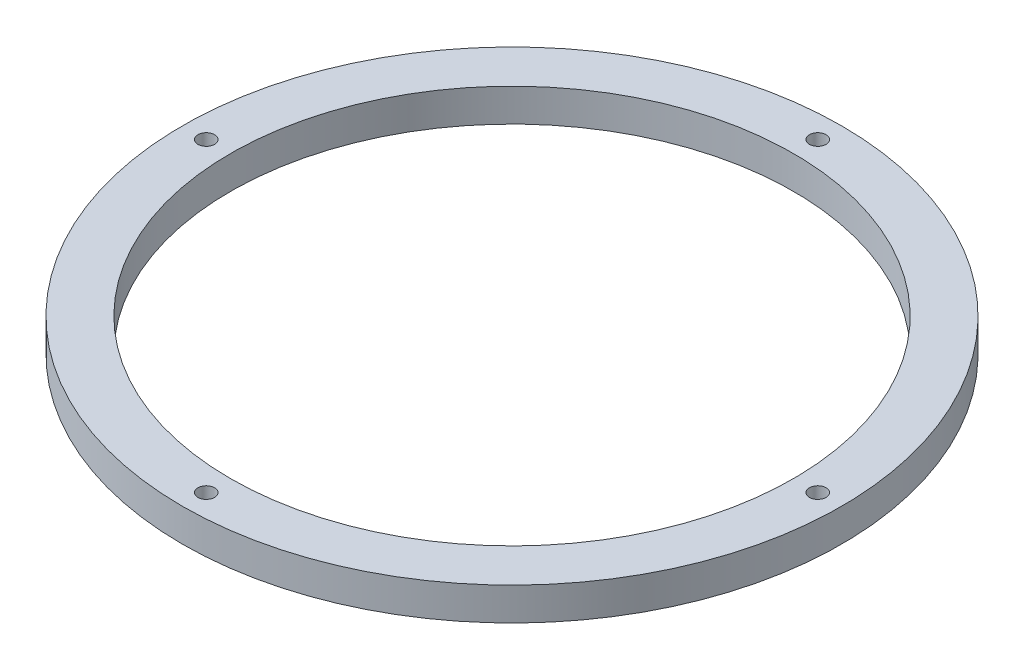
SolidWorks part; units mm, degrees
ref_plane "Front Plane" through (0, 0, 0) normal (0, 0, 1) x (1, 0, 0)
ref_plane "Top Plane" through (0, 0, 0) normal (0, 1, 0) x (1, 0, 0)
ref_plane "Right Plane" through (0, 0, 0) normal (1, 0, 0) x (0, 0, -1)
sketch "Sketch1" plane through (0, 0, 0) normal (0, 1, 0) x (1, 0, 0)
  circle A0 centre (0, 0) radius 100.375
  circle A5 centre (0, 0) radius 85.75
  dimension "D1" = 200.75
  dimension "D2" = 171.5
extrude "Boss-Extrude1" add sketch "Sketch1" along normal mid plane 10
sketch "Sketch2" plane through (0, 0, 0) normal (0, 1, 0) x (1, 0, 0)
  circle A0 centre (-93.125, 0) radius 1.27
  dimension "D2" = 2.54
  dimension "D1" = 93.125
extrude "Cut-Extrude1" cut sketch "Sketch2" against normal through all both and the other way through all
ref_axis "Axis1" through (0, 5.5, 0) along (0, -1, 0)
pattern_circular "CirPattern1" count 4 over 360 about axis through (0, 5.5, 0) along (0, -1, 0) of "Cut-Extrude1"
hole_wizard "CSK for #10 Flat Head Machine Screw (100)1" positions "3DSketch1" profile "Sketch3" countersink size "#10" standard "ANSI Inch" end condition through all
sketch3d "3DSketch1"
  line L0 (93.125, -5, 0) -> (93.125, 5, 0) construction
  line L1 (0, -5, -93.125) -> (0, 5, -93.125) construction
  line L2 (-93.125, -5, 0) -> (-93.125, 5, 0) construction
  line L3 (0, -5, 93.125) -> (0, 5, 93.125) construction
  point P0 (93.125, -5, 0)
  point P4 (0, -5, -93.125)
  point P8 (-93.125, -5, 0)
  point P12 (0, -5, 93.125)
sketch "Sketch3" plane through (93.125, -5, 0) normal (1, 0, 0) x (0, 0, -1)
  line L0 (0, 0) -> (0, 10)
  line L1 (0, 10) -> (2.5527, 10)
  line L2 (2.5527, 10) -> (2.5527, 1.9608)
  line L3 (2.5527, 1.9608) -> (4.8895, 0)
  line L5 (4.8895, 0) -> (0, 0)
  line L6 (-2.5527, 1.9608) -> (-4.8895, 0) construction
  line L11 (0, -6.35) -> (0, 107.95) construction
  dimension "Thru Hole Dia." = 5.1054
  dimension "Thru Hole Depth" = 10
  dimension "Near C'Sink Dia." = 9.779
  dimension "Near C'Sink Angle" = 100
equation "\"thicknes\"= 10mm"
equation "\"D1@Boss-Extrude1\"=\"thicknes\""
equation "\"id\"= 171.5mm"
equation "\"D2@Sketch1\"=\"id\""
equation "\"od\"= 200.75mm"
equation "\"D1@Sketch1\"=\"od\""
equation "\"hole_radius\"= \"hole_diameter\" / 2"
equation "\"D1@Sketch2\"=\"hole_radius\""
equation "\"hole_diameter\"= 186.25mm"
